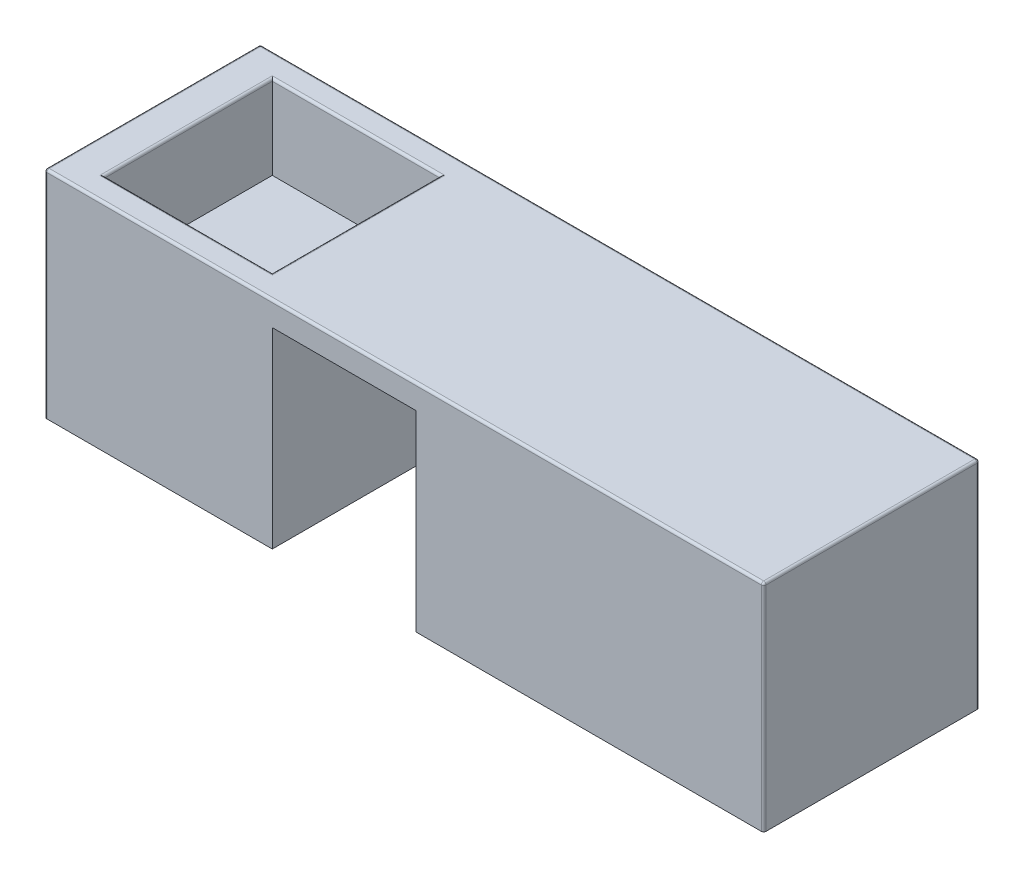
SolidWorks part; units mm, degrees
ref_plane "Front Plane" through (0, 0, 0) normal (0, 0, 1) x (1, 0, 0)
ref_plane "Top Plane" through (0, 0, 0) normal (0, 1, 0) x (1, 0, 0)
ref_plane "Right Plane" through (0, 0, 0) normal (1, 0, 0) x (0, 0, -1)
sketch "Sketch1" plane through (0, 0, 0) normal (0, 1, 0) x (1, 0, 0)
  line L1 (-1500, -450) -> (1500, -450)
  line L2 (-1500, -450) -> (-1500, 450)
  line L3 (-1500, 450) -> (1500, 450)
  line L4 (1500, -450) -> (1500, 450)
  line L5 (-1500, -450) -> (1500, 450) construction
  line L6 (-1500, 450) -> (1500, -450) construction
  point P0 (0, 0)
  dimension "D1" = 900
  dimension "D2" = 3000
extrude "Boss-Extrude1" add sketch "Sketch1" along normal blind 900
sketch "Sketch2" plane through (0, 900, 0) normal (0, 1, 0) x (1, 0, 0)
  line L0 (0, 0) -> (-1000, 0) construction
  line L6 (-650, -350) -> (-1350, -350)
  line L7 (-650, -350) -> (-650, 350)
  line L8 (-650, 350) -> (-1350, 350)
  line L9 (-1350, -350) -> (-1350, 350)
  line L10 (-650, -350) -> (-1350, 350) construction
  line L11 (-650, 350) -> (-1350, -350) construction
  dimension "D1" = 700
  dimension "D2" = 700
  dimension "D3" = 1000
sketch "Sketch3" plane through (0, 0, 450) normal (0, 0, 1) x (1, 0, 0)
  line L0 (1500, 450) -> (-250, 450) construction
  line L1 (1500, 900) -> (1500, 0) construction
  line L2 (-250, 800) -> (-250, 900) construction
  line L3 (50, 800) -> (-550, 800)
  line L4 (50, 800) -> (50, 0)
  line L6 (-550, 800) -> (-550, 0)
  line L7 (-1500, 0) -> (1500, 0) construction
  line L8 (-550, 800) -> (50, 0) construction
  line L9 (-1500, 900) -> (1500, 900) construction
  line L10 (-550, 0) -> (50, 800) construction
  dimension "D1" = 1750
  dimension "D2" = 600
  dimension "D3" = 100
extrude "Cut-Extrude2" cut sketch "Sketch3" against normal blind 800 and the other way through all flip side to cut
extrude "Cut-Extrude3" cut sketch "Sketch2" against normal blind 350
fillet "Fillet1" radius 10 8 edges at (0, 900, 450) (-1500, 900, 0) (0, 900, -450) (1500, 900, 0) (-650, 900, 0) (-1000, 900, -350) (-1350, 900, 0) (-1000, 900, 350)
fillet "Fillet2" radius 10 8 edges at (1497.0711, 897.0711, -447.0711) (1497.0711, 897.0711, 447.0711) (-1497.0711, 897.0711, -447.0711) (-1497.0711, 897.0711, 447.0711) (1500, 445, -450) (1500, 445, 450) (-1500, 445, -450) (-1500, 445, 450)
